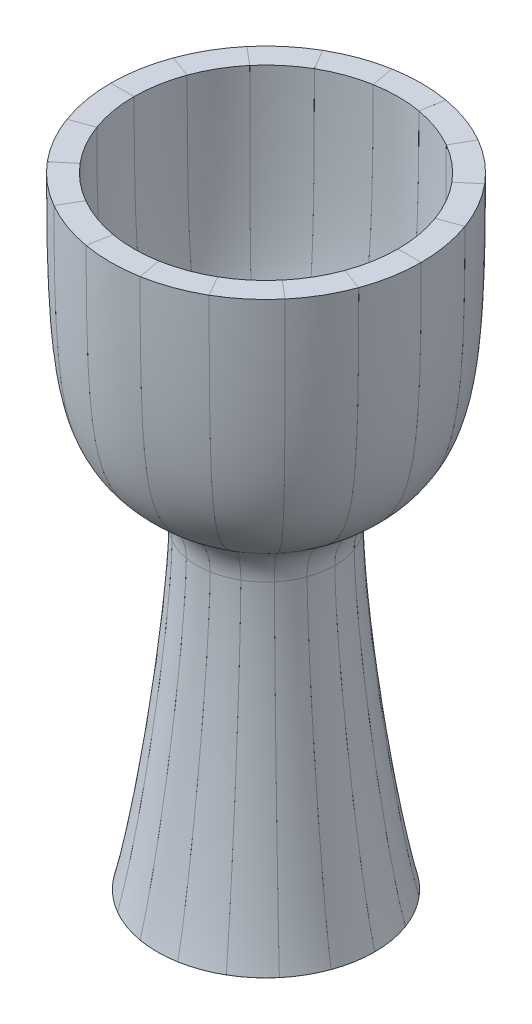
SolidWorks part; units mm, degrees
ref_plane "Front" through (0, 0, 0) normal (0, 0, 1) x (1, 0, 0)
ref_plane "Top" through (0, 0, 0) normal (0, 1, 0) x (1, 0, 0)
ref_plane "Right" through (0, 0, 0) normal (1, 0, 0) x (0, 0, -1)
sketch "Sketch1" plane through (0, 0, 0) normal (0, 0, 1) x (1, 0, 0)
  line L0 (0, 0) -> (0, 508) construction
  line L1 (0, 0) -> (69.4114, 0) construction
  line L2 (0, 508) -> (127, 508) construction
  line L3 (0, 279.4) -> (57.15, 279.4) construction
  line L4 (88.8992, 0.374) -> (70.3479, -4.1639)
  line L5 (70.4239, -4.1429) -> (70.3479, -4.1639)
  line L6 (88.8992, 0.501) -> (88.8992, 0.374)
  line L7 (107.95, 507.9952) -> (127, 508)
  arc A0 (72.4052, 289.3347) -> (56.2496, 257.793) centre (94.3476, 258.1876) ccw
  arc A1 (61.434, 304.9082) -> (37.2007, 257.5957) centre (94.3476, 258.1876) ccw
  conic Q0 (127, 508) -> (72.4052, 289.3347) control (127.0457, 327.8277) rho 0.652576
  conic Q1 (56.2496, 257.793) -> (88.8992, 0.501) control (57.6258, 124.9199) rho 0.340488
  spline S0 degree 1 poles (107.95, 507.9952) (61.434, 304.9082) knots 0 0 1 1 construction
  spline S1 degree 1 poles (37.2007, 257.5957) (70.4239, -4.1429) knots 0 0 1 1 construction
  spline S2 degree 3 poles (107.95, 507.9952) (107.9502, 507.1262) (107.9501, 505.3763) (107.9477, 501.9721) (107.9407, 497.8256) (107.9261, 493.0345) (107.8987, 486.8722) (107.8501, 479.5737) (107.7704, 471.3964) (107.6705, 463.7445) (107.5118, 454.177) (107.268, 443.2984) (106.9086, 431.6856) (106.4864, 421.2898) (106.0043, 411.9307) (105.2839, 400.6417) (104.241, 388.4547) (102.7638, 376.1875) (101.0559, 365.7783) (99.1067, 356.855) (96.8979, 349.1243) (94.3944, 342.3287) (91.5262, 336.2126) (88.1557, 330.499) (84.7246, 325.8183) (81.4041, 321.958) (78.5554, 318.9615) (75.2657, 315.8187) (72.0725, 313.0365) (69.183, 310.6841) (66.8307, 308.8491) (64.6937, 307.25) (62.8773, 305.9317) (61.9119, 305.2449) (61.434, 304.9082) knots 0 0 0 0 0.003906 0.007812 0.015625 0.023438 0.03125 0.046875 0.0625 0.078125 0.09375 0.125 0.15625 0.1875 0.21875 0.25 0.3125 0.375 0.4375 0.5 0.5625 0.625 0.6875 0.75 0.8125 0.84375 0.875 0.90625 0.9375 0.953125 0.96875 0.984375 0.992188 1 1 1 1
  spline S3 degree 3 poles (37.2007, 257.5957) (37.2087, 256.8185) (37.2297, 255.2925) (37.2954, 252.0137) (37.4217, 247.6366) (37.6492, 241.8693) (37.9571, 235.5859) (38.3495, 228.7755) (38.9903, 218.9941) (40.02, 205.4686) (41.6337, 187.3273) (43.6178, 167.5953) (45.9414, 146.7304) (48.5507, 125.2997) (51.3728, 103.9282) (54.3226, 83.2376) (57.3111, 63.7846) (60.255, 46.0116) (62.6122, 32.8516) (64.4141, 23.3876) (65.7194, 16.8251) (66.9748, 10.7971) (68.1609, 5.3744) (69.0078, 1.6952) (69.5689, -0.6627) (69.9562, -2.2646) (70.2397, -3.4102) (70.4239, -4.1429) knots 0 0 0 0 0.015625 0.03125 0.0625 0.09375 0.125 0.15625 0.1875 0.25 0.3125 0.375 0.4375 0.5 0.5625 0.625 0.6875 0.75 0.8125 0.84375 0.875 0.90625 0.9375 0.967319 0.975131 0.984375 1 1 1 1
  dimension "D4" = 38.1
  dimension "D1" = 508
  dimension "D2" = 88.9
  dimension "D3" = 127
  dimension "D5" = 279.4
  dimension "D7" = 0.127
  dimension "D6" = 19.05
revolve "Revolve1" add sketch "Sketch1" angle 360 about L0
ref_plane "Plane1" through (0, 508, 0) normal (0, 1, 0) x (1, 0, 0)
sketch "Sketch2" plane through (0, 508, 0) normal (0, 1, 0) x (1, 0, 0)
  line L0 (-18.9731, 0) -> (-18.9731, 0.0025)
  line L1 (-18.9731, 0) -> (-323.7731, 0.0204)
  line L2 (-18.9731, 0.0025) -> (-323.7731, 0.0229)
  line L3 (-323.7731, 0.0204) -> (-323.7731, 0.0229)
  line L4 (-17.8289, 6.4892) -> (-304.2403, 110.7561)
  line L5 (-304.2403, 110.7561) -> (-304.2394, 110.7585)
  line L6 (-17.8281, 6.4916) -> (-304.2394, 110.7585)
  line L7 (-17.8289, 6.4892) -> (-17.8281, 6.4916)
  line L8 (-14.5343, 12.1957) -> (-248.0115, 208.133)
  line L9 (-248.0115, 208.133) -> (-248.0099, 208.1349)
  line L10 (-14.5326, 12.1977) -> (-248.0099, 208.1349)
  line L11 (-14.5343, 12.1957) -> (-14.5326, 12.1977)
  line L12 (-9.4866, 16.4312) -> (-161.8689, 280.406)
  line L13 (-161.8689, 280.406) -> (-161.8667, 280.4072)
  line L14 (-9.4844, 16.4325) -> (-161.8667, 280.4072)
  line L15 (-9.4866, 16.4312) -> (-9.4844, 16.4325)
  line L16 (-3.2947, 18.6849) -> (-56.2025, 318.8579)
  line L17 (-56.2025, 318.8579) -> (-56.2, 318.8583)
  line L18 (-3.2922, 18.6853) -> (-56.2, 318.8583)
  line L19 (-3.2947, 18.6849) -> (-3.2922, 18.6853)
  line L20 (3.2947, 18.6849) -> (56.2427, 318.8508)
  line L21 (56.2427, 318.8508) -> (56.2452, 318.8503)
  line L22 (3.2972, 18.6845) -> (56.2452, 318.8503)
  line L23 (3.2947, 18.6849) -> (3.2972, 18.6845)
  line L24 (9.4866, 16.4312) -> (161.9042, 280.3856)
  line L25 (161.9042, 280.3856) -> (161.9064, 280.3843)
  line L26 (9.4888, 16.43) -> (161.9064, 280.3843)
  line L27 (9.4866, 16.4312) -> (9.4888, 16.43)
  line L28 (14.5343, 12.1957) -> (248.0377, 208.1017)
  line L29 (248.0377, 208.1017) -> (248.0394, 208.0998)
  line L30 (14.5359, 12.1938) -> (248.0394, 208.0998)
  line L31 (14.5343, 12.1957) -> (14.5359, 12.1938)
  line L32 (17.8289, 6.4892) -> (304.2542, 110.7178)
  line L33 (304.2542, 110.7178) -> (304.2551, 110.7154)
  line L34 (17.8298, 6.4868) -> (304.2551, 110.7154)
  line L35 (17.8289, 6.4892) -> (17.8298, 6.4868)
  line L36 (18.9731, 0) -> (323.7731, -0.0204)
  line L37 (323.7731, -0.0204) -> (323.7731, -0.0229)
  line L38 (18.9731, -0.0025) -> (323.7731, -0.0229)
  line L39 (18.9731, 0) -> (18.9731, -0.0025)
  line L40 (17.8289, -6.4892) -> (304.2403, -110.7561)
  line L41 (304.2403, -110.7561) -> (304.2394, -110.7585)
  line L42 (17.8281, -6.4916) -> (304.2394, -110.7585)
  line L43 (17.8289, -6.4892) -> (17.8281, -6.4916)
  line L44 (14.5343, -12.1957) -> (248.0115, -208.133)
  line L45 (248.0115, -208.133) -> (248.0099, -208.1349)
  line L46 (14.5326, -12.1977) -> (248.0099, -208.1349)
  line L47 (14.5343, -12.1957) -> (14.5326, -12.1977)
  line L48 (9.4866, -16.4312) -> (161.8689, -280.406)
  line L49 (161.8689, -280.406) -> (161.8667, -280.4072)
  line L50 (9.4844, -16.4325) -> (161.8667, -280.4072)
  line L51 (9.4866, -16.4312) -> (9.4844, -16.4325)
  line L52 (3.2947, -18.6849) -> (56.2025, -318.8579)
  line L53 (56.2025, -318.8579) -> (56.2, -318.8583)
  line L54 (3.2922, -18.6853) -> (56.2, -318.8583)
  line L55 (3.2947, -18.6849) -> (3.2922, -18.6853)
  line L56 (-3.2947, -18.6849) -> (-56.2427, -318.8508)
  line L57 (-56.2427, -318.8508) -> (-56.2452, -318.8503)
  line L58 (-3.2972, -18.6845) -> (-56.2452, -318.8503)
  line L59 (-3.2947, -18.6849) -> (-3.2972, -18.6845)
  line L60 (-9.4866, -16.4312) -> (-161.9042, -280.3856)
  line L61 (-161.9042, -280.3856) -> (-161.9064, -280.3843)
  line L62 (-9.4888, -16.43) -> (-161.9064, -280.3843)
  line L63 (-9.4866, -16.4312) -> (-9.4888, -16.43)
  line L64 (-14.5343, -12.1957) -> (-248.0377, -208.1017)
  line L65 (-248.0377, -208.1017) -> (-248.0394, -208.0998)
  line L66 (-14.5359, -12.1938) -> (-248.0394, -208.0998)
  line L67 (-14.5343, -12.1957) -> (-14.5359, -12.1938)
  line L68 (-17.8289, -6.4892) -> (-304.2542, -110.7178)
  line L69 (-304.2542, -110.7178) -> (-304.2551, -110.7154)
  line L70 (-17.8298, -6.4868) -> (-304.2551, -110.7154)
  line L71 (-17.8289, -6.4892) -> (-17.8298, -6.4868)
  circle A0 centre (0, 0) radius 18.9731 construction
  point P77 (0, 0)
  dimension "D1" = 0.0025
  dimension "D2" = 304.8
  dimension "D3" = 18
extrude "Cut-Extrude1" cut sketch "Sketch2" against normal through all
